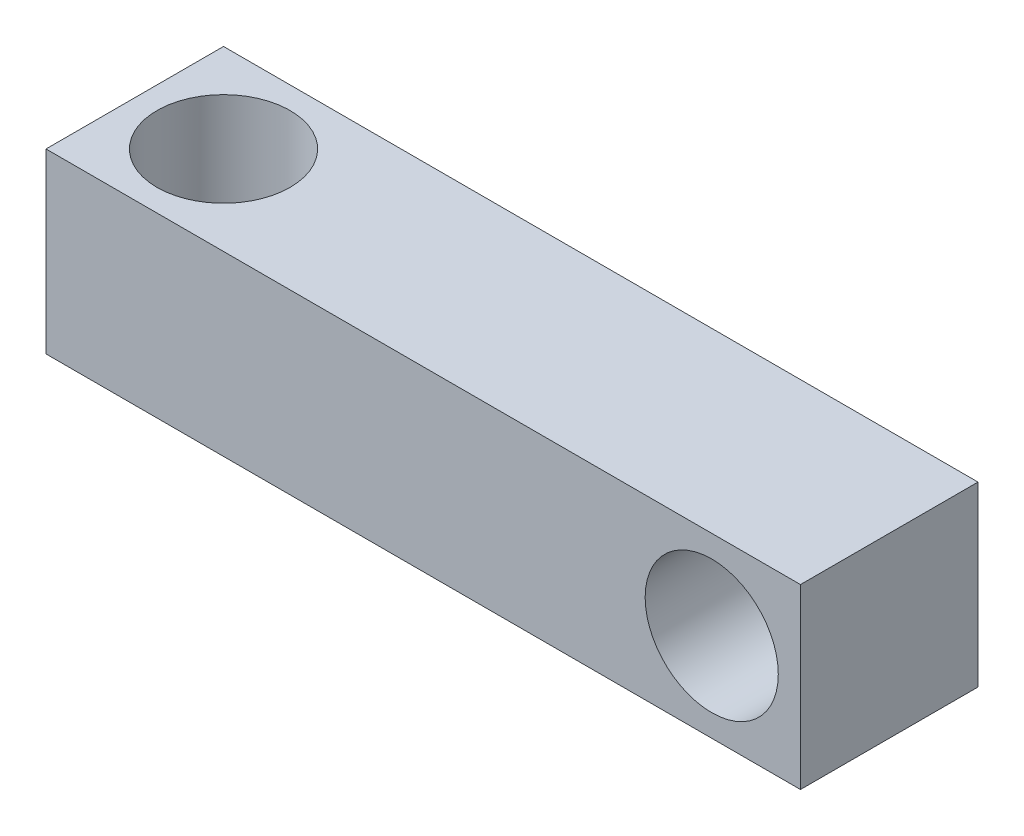
SolidWorks part; units mm, degrees
ref_plane "Alzado" through (0, 0, 0) normal (0, 0, 1) x (1, 0, 0)
ref_plane "Planta" through (0, 0, 0) normal (0, 1, 0) x (1, 0, 0)
ref_plane "Vista lateral" through (0, 0, 0) normal (1, 0, 0) x (0, 0, -1)
sketch "Croquis1" plane through (0, 0, 0) normal (0, 0, 1) x (1, 0, 0)
  line L0 (0, 11.7591) -> (42.5, 11.7591)
  line L1 (42.5, 11.7591) -> (42.5, -8.2409)
  line L2 (42.5, -8.2409) -> (-42.5, -8.2409)
  line L3 (-42.5, -8.2409) -> (-42.5, 11.7591)
  line L4 (-42.5, 11.7591) -> (0, 11.7591)
  dimension "D1" = 85
  dimension "D2" = 20
extrude "Saliente-Extruir1" add sketch "Croquis1" along normal mid plane 20
sketch "Croquis2" plane through (0, 0, 10) normal (0, 0, 1) x (1, 0, 0)
  line L0 (42.5, -8.2409) -> (42.5, 11.7591) construction
  circle A0 centre (32.5, 1.7591) radius 7.5
  dimension "D2" = 15
  dimension "D1" = 10
extrude "Cortar-Extruir1" cut sketch "Croquis2" against normal through all both and the other way through all
sketch "Croquis3" plane through (0, 11.7591, 0) normal (0, 1, 0) x (1, 0, 0)
  line L0 (-42.5, -10) -> (-42.5, 10) construction
  circle A0 centre (-32.5, 0) radius 7.5
  dimension "D2" = 15
  dimension "D1" = 10
extrude "Cortar-Extruir2" cut sketch "Croquis3" against normal through all both and the other way through all
